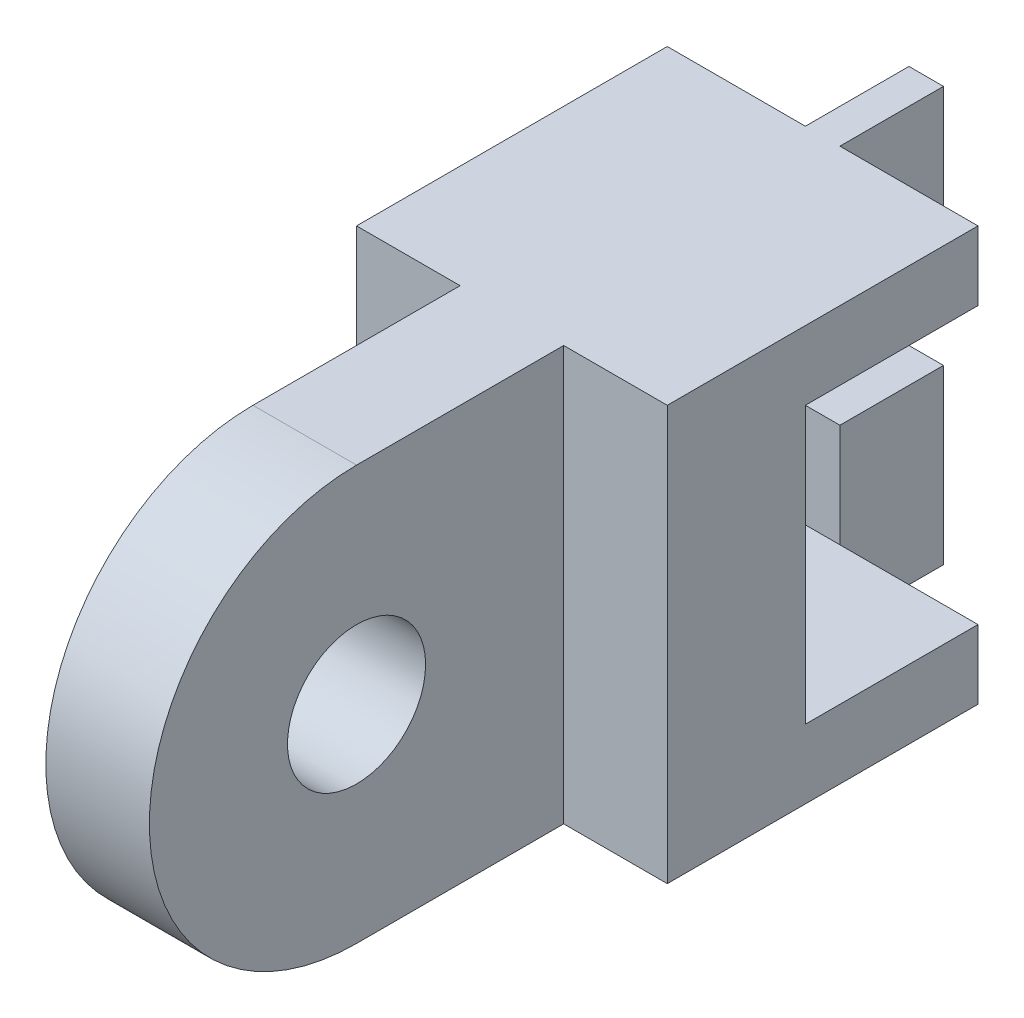
SolidWorks part; units mm, degrees
other "Markup1"
sketch "Sketch3" plane through (112.5, 150, -450) normal (0.9787, 0.0607, -0.1963) x (-0.204, 0.4027, -0.8923)
ref_plane "Front Plane" through (0, 0, 0) normal (0, 0, 1) x (1, 0, 0)
ref_plane "Top Plane" through (0, 0, 0) normal (0, 1, 0) x (1, 0, 0)
ref_plane "Right Plane" through (0, 0, 0) normal (1, 0, 0) x (0, 0, -1)
sketch "Sketch2" plane through (0, 0, 0) normal (1, 0, 0) x (0, 0, -1)
  line L0 (0, 150) -> (150, 150)
  line L1 (0, -150) -> (150, -150)
  line L2 (150, -150) -> (150, 150)
  line L3 (150, 150) -> (375, 150)
  line L4 (375, 150) -> (375, 100)
  line L5 (375, 100) -> (250, 100)
  line L6 (250, 100) -> (250, -100)
  line L7 (250, -100) -> (375, -100)
  line L8 (375, -100) -> (375, -150)
  line L9 (375, -150) -> (150, -150)
  line L10 (150, 150) -> (150, -150)
  line L11 (375, 150) -> (450, 150)
  line L12 (450, 150) -> (450, 75)
  line L13 (375, 100) -> (375, 75)
  line L14 (375, 75) -> (450, 75)
  line L15 (375, -100) -> (375, -25)
  line L16 (375, -25) -> (450, -25)
  line L17 (450, -25) -> (450, -150)
  line L18 (450, -150) -> (375, -150)
  arc A0 (0, 150) -> (0, -150) centre (0, 0) ccw
  circle A1 centre (0, 0) radius 50
  dimension "D1" = 150
  dimension "D2" = 100
  dimension "D3" = 150
  dimension "D4" = 225
  dimension "D5" = 225
  dimension "D6" = 50
  dimension "D7" = 50
  dimension "D8" = 100
  dimension "D9" = 75
  dimension "D10" = 75
  dimension "D11" = 75
  dimension "D12" = 125
extrude "Boss-Extrude1" add sketch "Sketch2" along normal blind 37.5 and the other way blind 37.5 contours L0 A0 L1 L2 A1 region at (0, 145.7574, -75)
extrude "Boss-Extrude2" add sketch "Sketch2<12>" along normal blind 112.5 and the other way blind 112.5 contours L9 L8 L7 L6 L5 L4 L3 L2 region at (0, 0, -233.0882)
sketch "Sketch2<12>" plane through (0, 0, 0) normal (1, 0, 0) x (0, 0, -1) same geometry as "Sketch2"
extrude "Boss-Extrude3" add sketch "Sketch2<13>" along normal blind 12.5 and the other way blind 12.5 contours L13 L14 L12 L11 L4 region at (0, 112.5, -412.5)
sketch "Sketch2<13>" plane through (0, 0, 0) normal (1, 0, 0) x (0, 0, -1) same geometry as "Sketch2"
extrude "Boss-Extrude4" add sketch "Sketch2<14>" along normal blind 12.5 and the other way blind 12.5 contours L18 L17 L16 L15 L8 region at (0, -87.5, -412.5)
sketch "Sketch2<14>" plane through (0, 0, 0) normal (1, 0, 0) x (0, 0, -1) same geometry as "Sketch2"
